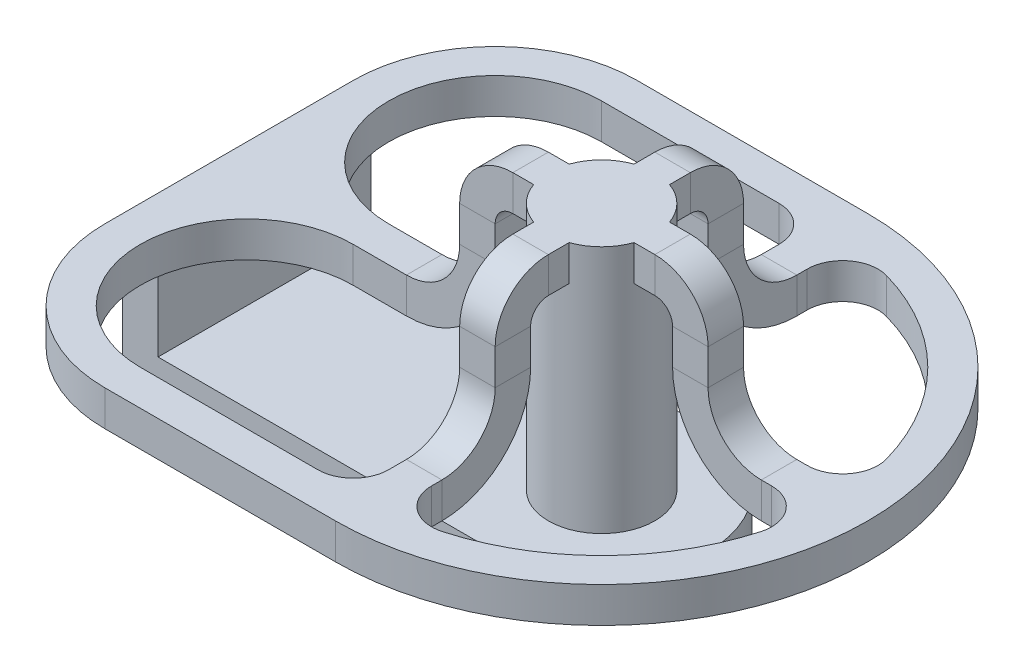
SolidWorks part; units mm, degrees
ref_plane "Ön Düzlem" through (0, 0, 0) normal (0, 0, 1) x (1, 0, 0)
ref_plane "Üst Düzlem" through (0, 0, 0) normal (0, 1, 0) x (1, 0, 0)
ref_plane "Sağ Düzlem" through (0, 0, 0) normal (1, 0, 0) x (0, 0, -1)
sketch "Çizim2" plane through (0, 0, 0) normal (0, 0, 1) x (1, 0, 0)
  line L0 (0, 0) -> (0, 30)
  line L1 (0, 30) -> (-10, 30)
  line L2 (-10, 30) -> (-10, -10)
  line L3 (-10, -10) -> (125, -10)
  line L4 (125, -10) -> (125, 0)
  line L5 (125, 0) -> (0, 0)
  dimension "D1" = 10
  dimension "D2" = 135
  dimension "D3" = 40
extrude "Yükseklik-Ekstrüzyon1" add sketch "Çizim2" along normal blind 60
fillet "Radyus1" radius 30 2 edges at (125, -5, 0) (125, -5, 60)
sketch "Çizim4" plane through (0, -10, 0) normal (0, -1, 0) x (1, 0, 0)
  circle A0 centre (95, 30) radius 15
  circle A1 centre (95, 30) radius 10
  dimension "D1" = 30
  dimension "D2" = 20
extrude "Yükseklik-Ekstrüzyon2" add sketch "Çizim4" against normal blind 70
sketch "Çizim5" plane through (0, 60, 0) normal (0, 1, 0) x (1, 0, 0)
  circle A0 centre (95, -30) radius 15
extrude "Yükseklik-Ekstrüzyon3" add sketch "Çizim5" along normal blind 10
sketch "Çizim7" plane through (0, 30, 0) normal (0, 1, 0) x (1, 0, 0)
  line L0 (-10, -60) -> (-10, 0) construction
  line L1 (30, 45) -> (95, 45)
  line L2 (-10, 5) -> (-10, -65)
  line L3 (30, -105) -> (95, -105)
  line L5 (30, -95) -> (80, -95)
  line L6 (30, 35) -> (80, 35)
  line L7 (30, -25) -> (80.8579, -25)
  line L8 (30, -35) -> (80.8579, -35)
  line L10 (0, 5) -> (0, -65) construction
  line L12 (95, -131.033) -> (95, 71.033) construction
  line L13 (-63.9204, -30) -> (253.9204, -30) construction
  line L14 (90, 25) -> (90, -15.8579)
  line L15 (30, 35) -> (95, 35) construction
  line L16 (100, -15.8579) -> (100, 22.915)
  line L17 (109.1421, -25) -> (147.915, -25)
  line L18 (90, -44.1421) -> (90, -85)
  line L19 (100, -44.1421) -> (100, -82.915)
  line L20 (104.8089, -35) -> (147.915, -35)
  line L21 (30, -95) -> (95, -95) construction
  arc A0 (95, -105) -> (95, 45) centre (95, -30) ccw
  arc A1 (-10, -65) -> (30, -105) centre (30, -65) ccw
  arc A2 (30, 45) -> (-10, 5) centre (30, 5) ccw
  arc A5 (112.7273, -92.5359) -> (157.5359, -47.7273) centre (95, -30) ccw
  arc A6 (30, 35) -> (30, -25) centre (30, 5) ccw
  arc A7 (30, 35) -> (0, 5) centre (30, 5) ccw construction
  arc A9 (0, -65) -> (30, -95) centre (30, -65) ccw construction
  arc A12 (30, -35) -> (0, -65) centre (30, -65) ccw
  arc A13 (0, -65) -> (30, -95) centre (30, -65) ccw
  arc A14 (109.1421, -35) -> (109.1421, -25) centre (95, -30) ccw
  arc A15 (90, 25) -> (80, 35) centre (80, 25) ccw
  arc A16 (95, -95) -> (95, 35) centre (95, -30) ccw construction
  arc A17 (100, 22.915) -> (112.7273, 32.5359) centre (110, 22.915) cw
  arc A18 (157.5359, -12.2727) -> (112.7273, 32.5359) centre (95, -30) ccw
  arc A19 (80, -95) -> (90, -85) centre (80, -85) ccw
  arc A20 (100, -82.915) -> (112.7273, -92.5359) centre (110, -82.915) ccw
  arc A21 (147.915, -35) -> (157.5359, -47.7273) centre (147.915, -45) cw
  arc A22 (90, -44.1421) -> (100, -44.1421) centre (95, -30) ccw
  arc A23 (80.8579, -25) -> (80.8579, -35) centre (95, -30) ccw
  arc A24 (100, -15.8579) -> (90, -15.8579) centre (95, -30) ccw
  arc A25 (147.915, -25) -> (157.5359, -12.2727) centre (147.915, -15) ccw
  point P6 (-10, -30)
  point P7 (-10, -30)
  point P13 (-10, 45)
  point P34 (95, -30)
  point P37 (95, -30)
  point P45 (159.8074, -25)
  line M40 (0, 0) -> (-10, 0)
  line M41 (-10, 0) -> (-10, -60)
  line M42 (-10, -60) -> (0, -60)
  line M43 (0, -60) -> (0, 0)
  dimension "D3" = 75
  dimension "D4" = 40
  dimension "D8" = 60
  dimension "D9" = 30
  dimension "D10" = 30
  dimension "D11" = 10
  dimension "D14" = 10
  dimension "D15" = 10
  dimension "D16" = 10
  dimension "D1" = 150
  dimension "D2" = 105
  dimension "D6" = 5
  dimension "D7" = 10
  dimension "D12" = 5
  dimension "D13" = 5
  dimension "D5" = 10
extrude "Yükseklik-Ekstrüzyon4" add sketch "Çizim7" against normal blind 10 contours L1 A2 L2 A1 L3 A0 A24 L16 A17 A18 L17 A14 L20 A21 A5 A20 L19 A22 L18 A19 L5 A13 A12 L8 A23 L7 A6 L6 A15 L14 M40 M43 M42 | M43 M40 M41 M42 region at (62.5, 30, -42.6569) region at (-5, 30, 30)
sketch "Çizim8" plane through (0, 30, 0) normal (0, 1, 0) x (1, 0, 0)
  line L0 (90, -44.1421) -> (90, -85) construction
  line L5 (30, -25) -> (80.8579, -25)
  line L6 (30, -25) -> (30, -35)
  line L7 (30, -35) -> (80.8579, -35)
  line L8 (147.915, -25) -> (147.915, -35)
  line L9 (100, 22.915) -> (90, 22.915)
  line L10 (100, 22.915) -> (100, -15.8579)
  line L11 (100, -82.915) -> (90, -82.915)
  line L12 (90, 22.915) -> (90, -15.8579)
  line L13 (109.1421, -35) -> (147.915, -35)
  line L14 (100, -44.1421) -> (100, -82.915)
  line L15 (109.1421, -25) -> (147.915, -25)
  line L16 (90, -44.1421) -> (90, -82.915)
  arc A0 (90, -44.1421) -> (100, -44.1421) centre (95, -30) ccw
  arc A1 (100, -15.8579) -> (90, -15.8579) centre (95, -30) ccw
  arc A2 (109.1421, -35) -> (109.1421, -25) centre (95, -30) ccw
  arc A3 (80.8579, -25) -> (80.8579, -35) centre (95, -30) ccw
extrude "Kes-Ekstrüzyon1" cut sketch "Çizim8" against normal blind 10
ref_plane "Düzlem1" through (0, 0, 30) normal (0, 0, 1) x (1, 0, 0)
sketch "Çizim10" plane through (0, 0, 30) normal (0, 0, 1) x (1, 0, 0)
  line L0 (95, 70) -> (115, 70)
  line L2 (130, 55) -> (130, 45)
  line L3 (157.5359, 30) -> (112.7273, 30) construction
  line L4 (145, 30) -> (147.915, 30)
  line L5 (110, 70) -> (80, 70) construction
  arc A0 (130, 45) -> (145, 30) centre (145, 45) ccw
  arc A1 (115, 70) -> (130, 55) centre (115, 55) cw
  point P2 (95, 70)
  point P12 (130, 30)
  dimension "D1" = 15
  dimension "D2" = 15
  dimension "D3" = 35
sketch "Çizim11" plane through (147.915, 0, 0) normal (-1, 0, 0) x (0, 0, 1)
  line L1 (35, 30) -> (25, 30)
  line L2 (35, 30) -> (35, 20)
  line L3 (35, 20) -> (25, 20)
  line L4 (25, 30) -> (25, 20)
sweep "Süpür1" add profiles "Çizim11" path "Çizim10"
pattern_circular "Dairesel Kaplama3" count 4 over 360 about axis through (95, 70, 30) along (0, 1, 0) of "Süpür1"
sketch "Çizim13" plane through (30, 0, 0) normal (1, 0, 0) x (0, 0, -1)
  line L1 (-35, 30) -> (-25, 30)
  line L2 (-35, 30) -> (-35, 20)
  line L3 (-35, 20) -> (-25, 20)
  line L4 (-25, 30) -> (-25, 20)
extrude "Yükseklik-Ekstrüzyon5" add sketch "Çizim13" along normal up to surface (12.085 mm away) up to face at (42.085, 25, 30)
sketch "Çizim14" plane through (0, -10, 0) normal (0, -1, 0) x (1, 0, 0)
  circle A0 centre (95, 30) radius 10
  dimension "D1" = 20
extrude "Kes-Ekstrüzyon2" cut sketch "Çizim14" against normal blind 10
